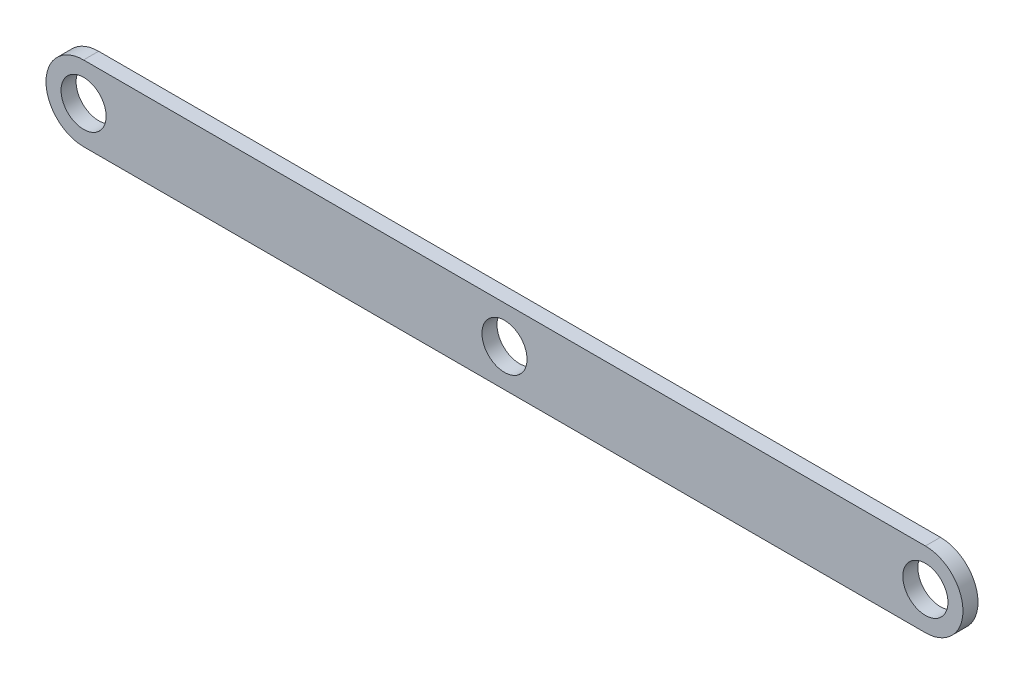
SolidWorks part; units mm, degrees
material "ALUMINUM 6061"
ref_plane "Front Plane" through (0, 0, 0) normal (0, 0, 1) x (1, 0, 0)
ref_plane "Top Plane" through (0, 0, 0) normal (0, 1, 0) x (1, 0, 0)
ref_plane "Right Plane" through (0, 0, 0) normal (1, 0, 0) x (0, 0, -1)
sketch "Sketch1" plane through (0, 0, 0) normal (0, 0, 1) x (1, 0, 0)
  line L0 (-88.9, 0) -> (88.9, 0) construction
  line L1 (-88.9, 7.9375) -> (88.9, 7.9375)
  line L2 (-88.9, -7.9375) -> (88.9, -7.9375)
  arc A0 (-88.9, 7.9375) -> (-88.9, -7.9375) centre (-88.9, 0) ccw
  arc A1 (88.9, -7.9375) -> (88.9, 7.9375) centre (88.9, 0) ccw
  circle A2 centre (-88.9, 0) radius 4.7625
  circle A3 centre (88.9, 0) radius 4.7625
  circle A4 centre (0, 0) radius 4.7625
  point P2 (0, 0)
  dimension "D3" = 9.525
  dimension "D1" = 177.8
  dimension "D2" = 15.875
extrude "Boss-Extrude1" add sketch "Sketch1" along normal blind 3.175
move or copy body "Body-Move/Copy1" [suppressed] bodies to move or copy 101
